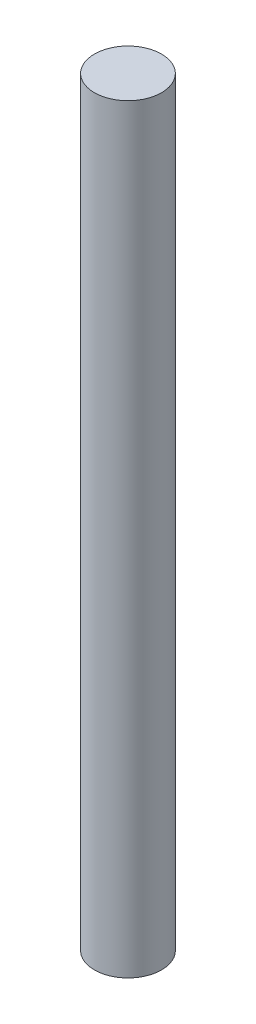
SolidWorks part; units mm, degrees
ref_plane "Front" through (0, 0, 0) normal (0, 0, 1) x (1, 0, 0)
ref_plane "Top" through (0, 0, 0) normal (0, 1, 0) x (1, 0, 0)
ref_plane "Right" through (0, 0, 0) normal (1, 0, 0) x (0, 0, -1)
ref_axis "X" through (-80.9, 0, 0) along (1, 0, 0)
ref_axis "Y" through (0, -50, 0) along (0, 1, 0)
ref_axis "Z" through (0, 0, -80.9) along (0, 0, 1)
sketch "Sketch1" plane through (0, 0, 0) normal (0, 1, 0) x (1, 0, 0)
  circle A0 centre (0, 0) radius 1.5
  dimension "D1" = 3
extrude "Boss-Extrude1" add sketch "Sketch1" along normal mid plane 34
